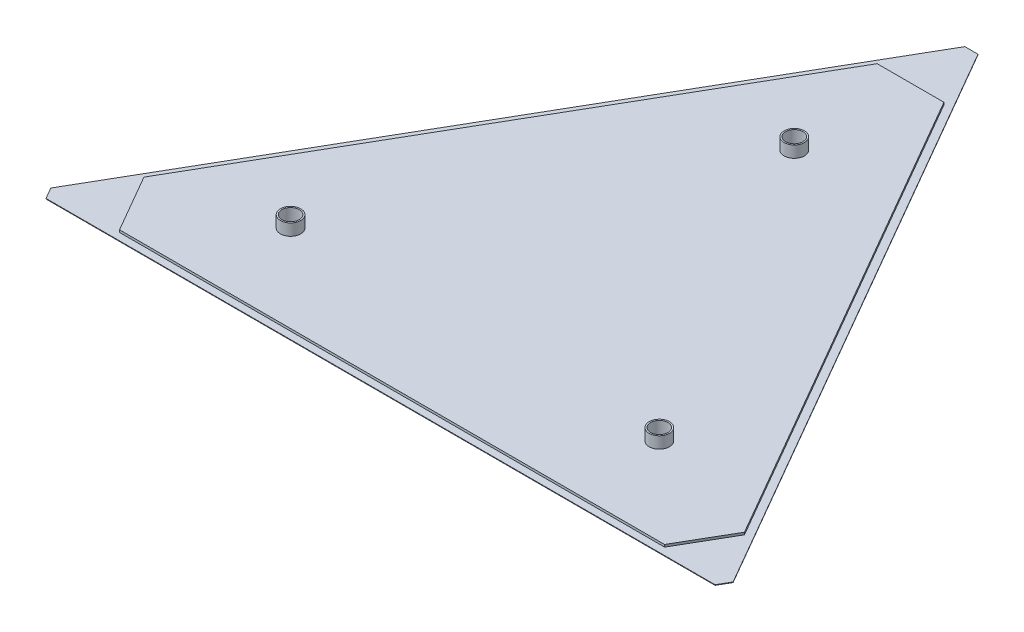
SolidWorks part; units mm, degrees
ref_plane "Front Plane" through (0, 0, 0) normal (0, 0, 1) x (1, 0, 0)
ref_plane "Top Plane" through (0, 0, 0) normal (0, 1, 0) x (1, 0, 0)
ref_plane "Right Plane" through (0, 0, 0) normal (1, 0, 0) x (0, 0, -1)
sketch "Sketch1" plane through (0, 0, 0) normal (0, 1, 0) x (1, 0, 0)
  line L1 (347.2736, 23.6092) -> (347.2736, 3.6092) construction
  line L2 (428.1137, -116.4172) -> (410.7932, -106.4172) construction
  line L8 (243.3042, -116.4848) -> (254.8093, -136.4089)
  line L10 (266.4391, -116.428) -> (283.7585, -106.4261) construction
  line L13 (452.6999, -118.9847) -> (442.6021, -136.4093)
  line L19 (231.9812, -138.9144) -> (229.7127, -134.9863)
  line L21 (344.9807, 64.6634) -> (229.7127, -134.9863)
  line L22 (349.5168, 64.6634) -> (344.9807, 64.6634)
  line L27 (464.7848, -134.9867) -> (462.5171, -138.9144)
  line L28 (462.5171, -138.9144) -> (231.9812, -138.9144)
  line L35 (335.7675, 43.666) -> (243.3042, -116.4848)
  line L36 (358.7782, 43.666) -> (335.7675, 43.666)
  line L62 (452.6999, -118.9847) -> (358.7782, 43.666)
  line L63 (442.6021, -136.4093) -> (254.8093, -136.4089)
  line L69 (464.7848, -134.9867) -> (349.5168, 64.6634)
  circle A1 centre (347.2736, 3.6092) radius 1.5
  circle A2 centre (283.7585, -106.4261) radius 1.5
  circle A3 centre (410.7932, -106.4172) radius 1.5
  circle A4 centre (347.2736, 3.6092) radius 3
  circle A5 centre (410.7932, -106.4172) radius 3
  circle A6 centre (283.7585, -106.4261) radius 3
  circle A7 centre (347.2736, 3.6092) radius 3.5
  circle A8 centre (410.7932, -106.4172) radius 3.5
  circle A9 centre (283.7585, -106.4261) radius 3.5
  point P12 (0, 0)
  dimension "D1" = 20
  dimension "D2" = 3
  dimension "D5" = 3
  dimension "D6" = 3
  dimension "D7" = 6
  dimension "D8" = 6
  dimension "D9" = 6
  dimension "D10" = 7
  dimension "D11" = 7
  dimension "D12" = 7
  dimension "D3" = 20
  dimension "D4" = 20
extrude "Boss-Extrude1" add sketch "Sketch1" along normal blind 0.2 contours A6 | A4 | A2 | A5 | A3 | A1 | L69 L22 L21 L19 L28 L27 | L8 L63 L13 L62 L36 L35
extrude "Boss-Extrude2" add sketch "Sketch1<14>" along normal blind 1
sketch "Sketch1<14>" plane through (0, 0, 0) normal (0, 1, 0) x (1, 0, 0) same geometry as "Sketch1"
extrude "Boss-Extrude4" add sketch "Sketch1<17>" along normal blind 5 contours A9 A6 | A8 A5 | A7 A4 region at (343.8726, 0, -3.6092) region at (407.3921, 0, 106.4172) region at (280.3575, 0, 106.4261)
sketch "Sketch1<17>" plane through (0, 0, 0) normal (0, 1, 0) x (1, 0, 0) same geometry as "Sketch1"
